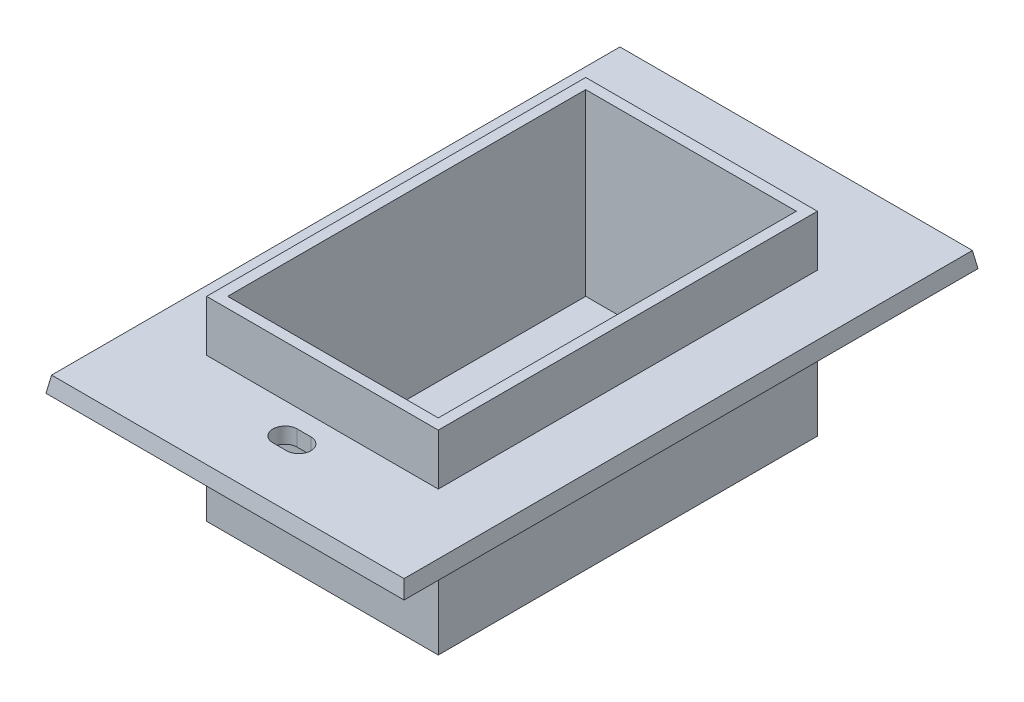
SolidWorks part; units mm, degrees
ref_plane "Front Plane" through (0, 0, 0) normal (0, 0, 1) x (1, 0, 0)
ref_plane "Top Plane" through (0, 0, 0) normal (0, 1, 0) x (1, 0, 0)
ref_plane "Right Plane" through (0, 0, 0) normal (1, 0, 0) x (0, 0, -1)
sketch "Sketch1" plane through (0, 0, 0) normal (0, 1, 0) x (1, 0, 0)
  line L1 (0, 0) -> (44, 0)
  line L2 (0, 0) -> (0, 72)
  line L3 (0, 72) -> (44, 72)
  line L4 (44, 0) -> (44, 72)
  dimension "D1" = 44
  dimension "D2" = 72
extrude "Boss-Extrude1" add sketch "Sketch1" along normal blind 3
sketch "Sketch2" plane through (0, 3, 0) normal (0, 1, 0) x (1, 0, 0)
  line L0 (2, 36) -> (0, 36) construction
  line L1 (0, 0) -> (44, 0)
  line L2 (0, 0) -> (0, 72)
  line L3 (0, 72) -> (44, 72)
  line L4 (44, 0) -> (44, 72)
  line L5 (2, 2) -> (42, 2)
  line L6 (2, 2) -> (2, 70)
  line L7 (2, 70) -> (42, 70)
  line L8 (42, 2) -> (42, 70)
  line L9 (22, 2) -> (22, 0) construction
  dimension "D1" = 40
  dimension "D2" = 68
extrude "Boss-Extrude2" add sketch "Sketch2" along normal blind 34
ref_plane "Plane1" through (0, 24.3, 0) normal (0, 1, 0) x (1, 0, 0)
sketch "Sketch3" plane through (0, 24.3, 0) normal (0, 1, 0) x (1, 0, 0)
  line L0 (0, 0) -> (44, 0) construction
  line L1 (44, 0) -> (44, 72) construction
  line L2 (44, 72) -> (0, 72) construction
  line L3 (20.7, 77.8) -> (23.3, 77.8) construction
  line L4 (0, 72) -> (0, 0) construction
  line L5 (22, 0) -> (22, -11.1) construction
  line L6 (0, 36) -> (44, 36) construction
  line L12 (0, 72) -> (44, 72)
  line L13 (20.7, -5.8) -> (23.3, -5.8) construction
  line L14 (20.7, -3.5) -> (23.3, -3.5)
  line L15 (20.7, -8.1) -> (23.3, -8.1)
  line L16 (18.4, -5.8) -> (25.6, -5.8) construction
  line L17 (20.7, 75.5) -> (23.3, 75.5)
  line L18 (20.7, 80.1) -> (23.3, 80.1)
  line L19 (18.4, 77.8) -> (25.6, 77.8) construction
  line L20 (0, 72) -> (0, 0)
  line L21 (0, 0) -> (44, 0)
  line L22 (22, 72) -> (22, 83.1) construction
  line L27 (44, 72) -> (44, 0)
  line L28 (56, -18.5) -> (-12, -18.5)
  line L29 (56, -18.5) -> (56, 90.5)
  line L30 (56, 90.5) -> (-12, 90.5)
  line L31 (-12, -18.5) -> (-12, 90.5)
  line L32 (56, -18.5) -> (-12, 90.5) construction
  line L33 (56, 90.5) -> (-12, -18.5) construction
  arc A0 (20.7, -3.5) -> (20.7, -8.1) centre (20.7, -5.8) ccw
  arc A1 (23.3, -8.1) -> (23.3, -3.5) centre (23.3, -5.8) ccw
  arc A2 (20.7, 75.5) -> (20.7, 80.1) centre (20.7, 77.8) cw
  arc A3 (23.3, 80.1) -> (23.3, 75.5) centre (23.3, 77.8) cw
  point P9 (22, -5.55)
  point P10 (22, 36)
  point P19 (22, -5.8)
  point P28 (22, 77.8)
  point P41 (22, 77.55)
  dimension "D1" = 68
  dimension "D2" = 4.6
  dimension "D3" = 39.5
  dimension "D4" = 2.6
  dimension "D5" = 109
extrude "Boss-Extrude3" add sketch "Sketch3" along normal blind 3
chamfer "Chamfer1" distance 3 angle 10 4 edges at (22, 27.3, -90.5) (-12, 27.3, -36) (22, 27.3, 18.5) (56, 27.3, -36) first distance on face at (22, 25.8, -90.5) first distance on face at (-12, 25.8, -36) first distance on face at (22, 25.8, 18.5) first distance on face at (56, 25.8, -36)
